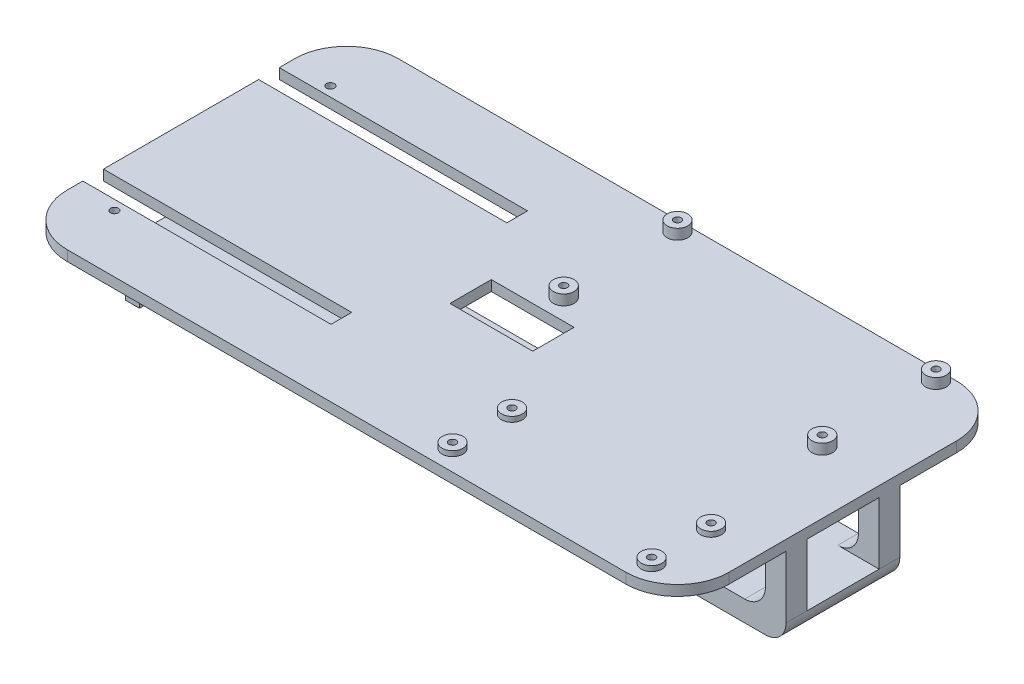
SolidWorks part; units mm, degrees
material "Polycarbonate"
ref_plane "Front Plane" through (0, 0, 0) normal (0, 0, 1) x (1, 0, 0)
ref_plane "Top Plane" through (0, 0, 0) normal (0, 1, 0) x (1, 0, 0)
ref_plane "Right Plane" through (0, 0, 0) normal (1, 0, 0) x (0, 0, -1)
sketch "Sketch1" plane through (0, 0, 0) normal (0, 1, 0) x (1, 0, 0)
  line L1 (-101.6, 17.4625) -> (101.6, 17.4625)
  line L2 (-101.6, 17.4625) -> (-101.6, -17.4625)
  line L3 (-101.6, -17.4625) -> (101.6, -17.4625)
  line L4 (101.6, 17.4625) -> (101.6, -17.4625)
  line L5 (-101.6, 17.4625) -> (101.6, -17.4625) construction
  line L6 (-101.6, -17.4625) -> (101.6, 17.4625) construction
  point P0 (0, 0)
  dimension "D1" = 34.925
  dimension "D2" = 203.2
extrude "Boss-Extrude1" add sketch "Sketch1" along normal blind 6.35
sketch "Sketch2" plane through (0, 6.35, 0) normal (0, 1, 0) x (1, 0, 0)
  line L0 (101.6, -17.4625) -> (101.6, 17.4625) construction
  line L1 (-101.6, -50.8) -> (101.6, -50.8)
  line L2 (-101.6, -50.8) -> (-101.6, 50.8)
  line L3 (-101.6, 50.8) -> (101.6, 50.8)
  line L4 (101.6, -50.8) -> (101.6, 50.8)
  line L5 (-101.6, -50.8) -> (101.6, 50.8) construction
  line L6 (-101.6, 50.8) -> (101.6, -50.8) construction
  point P0 (0, 0)
  dimension "D1" = 101.6
extrude "Boss-Extrude3" add sketch "Sketch2" along normal blind 3.175 from offset 19.05 separate body
sketch "Sketch3" plane through (0, 6.35, 0) normal (0, 1, 0) x (1, 0, 0)
  line L1 (101.6, -17.4625) -> (95.25, -17.4625)
  line L2 (101.6, -17.4625) -> (101.6, -11.1125)
  line L3 (101.6, -11.1125) -> (95.25, -11.1125)
  line L4 (95.25, -17.4625) -> (95.25, -11.1125)
  line L5 (101.6, 17.4625) -> (95.25, 17.4625)
  line L6 (101.6, 17.4625) -> (101.6, 11.1125)
  line L7 (101.6, 11.1125) -> (95.25, 11.1125)
  line L8 (95.25, 17.4625) -> (95.25, 11.1125)
  line L9 (-93.6625, -15.0813) -> (-87.3125, -15.0812)
  line L10 (-93.6625, -15.0813) -> (-93.6625, -10.3188)
  line L11 (-93.6625, -10.3188) -> (-87.3125, -10.3188)
  line L12 (-87.3125, -15.0812) -> (-87.3125, -10.3188)
  line L13 (-101.6, 17.4625) -> (-101.6, -17.4625) construction
  line L15 (-93.6625, 15.0813) -> (-87.3125, 15.0813)
  line L16 (-93.6625, 15.0813) -> (-93.6625, 10.3188)
  line L17 (-93.6625, 10.3188) -> (-87.3125, 10.3188)
  line L18 (-87.3125, 15.0813) -> (-87.3125, 10.3188)
  line L21 (-101.6, -17.4625) -> (101.6, -17.4625) construction
  line L22 (101.6, 17.4625) -> (-101.6, 17.4625) construction
  point P16 (-90.4875, -10.3188)
  point P23 (-87.3125, 12.7)
  point P25 (-90.4875, 15.0813)
  point P29 (-93.6625, -12.7)
  line M9 (101.6, -17.4625) -> (101.6, 17.4625)
  line M10 (101.6, 17.4625) -> (-101.6, 17.4625)
  line M12 (-101.6, -17.4625) -> (101.6, -17.4625)
  dimension "D1" = 6.35
  dimension "D2" = 11.1125
  dimension "D3" = 6.35
  dimension "D4" = 4.7625
  dimension "D5" = 11.1125
  dimension "D6" = 6.35
  dimension "D7" = 4.7625
  dimension "D8" = 4.7625
  dimension "D9" = 4.7625
extrude "Boss-Extrude4" add sketch "Sketch3" along normal up to next contours L4 L3 M12 M9 | L8 L7 M10 M9 region at (98.425, 6.35, -14.2875) region at (98.425, 6.35, 14.2875)
sketch "Sketch4" plane through (0, 28.575, 0) normal (0, 1, 0) x (1, 0, 0)
  line L0 (-101.6, 50.8) -> (-101.6, -50.8) construction
  line L1 (-101.6, -50.8) -> (101.6, -50.8) construction
  line L2 (-101.6, -30.1625) -> (-25.4, -30.1625)
  line L3 (-101.6, -30.1625) -> (-101.6, -23.8125)
  line L4 (-101.6, -23.8125) -> (-25.4, -23.8125)
  line L5 (-25.4, -30.1625) -> (-25.4, -23.8125)
  line L6 (0, 0) -> (-101.6, 0) construction
  line L7 (-25.4, 30.1625) -> (-25.4, 23.8125)
  line L8 (-101.6, 30.1625) -> (-25.4, 30.1625)
  line L9 (-101.6, 30.1625) -> (-101.6, 23.8125)
  line L10 (-101.6, 23.8125) -> (-25.4, 23.8125)
  dimension "D1" = 20.6375
  dimension "D2" = 6.35
  dimension "D3" = 76.2
extrude "Cut-Extrude1" cut sketch "Sketch4" against normal blind 3.175
sketch "Sketch5" plane through (101.6, 0, 0) normal (1, 0, 0) x (0, 0, -1)
  line L1 (14.8971, 25.4) -> (14.8971, 36.7665)
  line L3 (17.4625, 25.4) -> (17.4625, 0) construction
  line L5 (-10.1346, 32.004) -> (-10.1346, 25.4)
  line L6 (10.0076, 25.4) -> (10.0076, 32.004)
  line L7 (-14.8971, 25.4) -> (-10.1346, 25.4)
  line L8 (10.0076, 25.4) -> (14.8971, 25.4)
  line L11 (-50.8, 25.4) -> (-17.4625, 25.4) construction
  line L12 (-46.0375, 25.4) -> (-42.8625, 25.4)
  line L13 (-46.0375, 25.4) -> (-46.0375, 22.225)
  line L14 (-46.0375, 22.225) -> (-42.8625, 22.225)
  line L15 (-42.8625, 25.4) -> (-42.8625, 22.225)
  line L16 (-11.1125, 6.35) -> (11.1125, 6.35) construction
  line L21 (17.4625, 25.4) -> (50.8, 25.4) construction
  line L22 (-14.8971, 25.4) -> (-14.8971, 36.7665)
  line L23 (-50.8, 28.575) -> (-50.8, 25.4) construction
  line L24 (42.8625, 25.4) -> (46.0375, 25.4)
  line L25 (42.8625, 25.4) -> (42.8625, 22.225)
  line L26 (42.8625, 22.225) -> (46.0375, 22.225)
  line L27 (46.0375, 25.4) -> (46.0375, 22.225)
  line L28 (-14.8971, 36.7665) -> (-3.7846, 36.7665)
  line L29 (50.8, 28.575) -> (50.8, 25.4) construction
  line L30 (-3.7846, 36.7665) -> (-3.7846, 32.004)
  line L31 (-3.7846, 32.004) -> (-10.1346, 32.004)
  line L32 (14.8971, 36.7665) -> (3.6576, 36.7665)
  line L33 (3.6576, 36.7665) -> (3.6576, 32.004)
  line L34 (3.6576, 32.004) -> (10.0076, 32.004)
  line L35 (-17.4625, 25.4) -> (-17.4625, 0) construction
  point P31 (-46.0375, 23.8125)
  point P38 (17.4625, 12.7)
  dimension "D2" = 6.604
  dimension "D3" = 2.5654
  dimension "D4" = 3.175
  dimension "D5" = 3.175
  dimension "D6" = 4.7625
  dimension "D7" = 4.7625
  dimension "D8" = 3.175
  dimension "D9" = 3.175
  dimension "D10" = 19.05
  dimension "D11" = 4.7625
  dimension "D12" = 4.7625
  dimension "D13" = 6.35
  dimension "D14" = 4.8895
  dimension "D15" = 6.35
  dimension "D16" = 4.7625
  dimension "D17" = 2.5654
extrude "Boss-Extrude5" add sketch "Sketch5" against normal blind 3.175 from offset 190.5 contours L15 L14 L13 L12 | L27 L26 L25 L24 offset against normal yes
hole_wizard "#2 Clearance Hole1" positions "Sketch7" profile "Sketch8" hole size "#2" standard "ANSI Inch" end condition through all
sketch "Sketch7" plane through (0, 25.4, 0) normal (0, -1, 0) x (-1, 0, 0)
  line L12 (25.4, 30.1625) -> (101.6, 30.1625) construction
  line L13 (101.6, 50.8) -> (101.6, 30.1625) construction
  line L14 (101.6, -30.1625) -> (101.6, -50.8) construction
  line L15 (101.6, -30.1625) -> (25.4, -30.1625) construction
  point P20 (88.9, 33.147)
  point P69 (88.9, -33.147)
  dimension "D1" = 2.9845
  dimension "D2" = 12.7
  dimension "D3" = 12.7
  dimension "D4" = 2.9845
sketch "Sketch8" plane through (-88.9, 25.4, -33.147) normal (1, 0, 0) x (0, 0, -1)
  line L0 (0, 0) -> (0, 3.175)
  line L1 (0, 3.175) -> (1.2192, 3.175)
  line L2 (1.2192, 3.175) -> (1.2192, 0)
  line L5 (1.2192, 0) -> (0, 0)
  line L11 (0, -6.35) -> (0, 107.95) construction
  dimension "Thru Hole Dia." = 2.4384
  dimension "Thru Hole Depth" = 3.175
fillet "Fillet1" radius 15.875 2 edges at (101.6, 26.9875, -50.8) (101.6, 26.9875, 50.8)
fillet "Fillet2" radius 6.35 3 edges at (95.25, 6.35, 14.2875) (95.25, 6.35, -14.2875) (101.6, 0, 0)
hole_wizard "#4-40 Tapped Hole2" positions "Sketch12" profile "Sketch14" tap size "#4-40" standard "ANSI Inch" end condition through all
sketch "Sketch12" plane through (0, 25.4, 0) normal (0, -1, 0) x (-1, 0, 0)
  line L0 (-26.1937, -44.45) -> (-87.3125, -44.45) construction
  line L2 (101.6, -50.8) -> (-85.725, -50.8) construction
  line L3 (-101.6, -34.925) -> (-101.6, -17.4625) construction
  line L4 (-26.1937, -44.45) -> (-26.1937, -26.1937) construction
  line L6 (-26.1937, -26.1937) -> (-87.3125, -26.1938) construction
  line L7 (-87.3125, -26.1938) -> (-87.3125, -44.45) construction
  line L8 (101.6, -50.8) -> (-85.725, -50.8) construction
  point P0 (-87.3125, -44.45)
  point P3 (-87.3125, -26.1938)
  point P6 (-26.1937, -26.1937)
  point P9 (-26.1937, -44.45)
  dimension "D1" = 61.1187
  dimension "D2" = 6.35
  dimension "D3" = 14.2875
  dimension "D4" = 24.6062
sketch "Sketch14" plane through (87.3125, 25.4, 44.45) normal (1, 0, 0) x (0, 0, -1)
  line L0 (0, 0) -> (0, 3.175)
  line L1 (0, 3.175) -> (1.1303, 3.175)
  line L2 (1.1303, 3.175) -> (1.1303, 0)
  line L5 (1.1303, 0) -> (0, 0)
  line L11 (0, -6.35) -> (0, 107.95) construction
  dimension "Thru Tap Drill Dia." = 2.2606
  dimension "Thru Tap Drill Depth" = 3.175
cosmetic thread "Hole Thread5" parameters "D2"=2.8448
cosmetic thread "Hole Thread6" parameters "D2"=2.8448
cosmetic thread "Hole Thread7" parameters "D2"=2.8448
cosmetic thread "Hole Thread8" parameters "D2"=2.8448
sketch "Sketch15" plane through (0, 25.4, 0) normal (0, -1, 0) x (1, 0, 0)
  circle A0 centre (26.1937, 44.45) radius 3.175
  circle A1 centre (87.3125, 44.45) radius 3.175
  circle A2 centre (87.3125, 26.1938) radius 3.175
  circle A3 centre (26.1937, 26.1937) radius 3.175
  dimension "D1" = 6.35
extrude "Boss-Extrude6" add sketch "Sketch15" against normal blind 1.5875 from surface starting at face at (87.3125, 28.575, 43.3197)
hole_wizard "#4-40 Tapped Hole4" positions "Sketch19" profile "Sketch20" tap size "#4-40" standard "ANSI Inch" end condition through all
sketch "Sketch19" plane through (0, 28.575, 0) normal (0, -1, 0) x (-1, 0, 0)
  point P0 (-87.3125, -44.45)
  point P3 (-87.3125, -26.1938)
  point P6 (-26.1937, -26.1937)
  point P9 (-26.1937, -44.45)
sketch "Sketch20" plane through (87.3125, 28.575, 44.45) normal (1, 0, 0) x (0, 0, -1)
  line L0 (0, 0) -> (0, 1.5875)
  line L1 (0, 1.5875) -> (1.1303, 1.5875)
  line L2 (1.1303, 1.5875) -> (1.1303, 0)
  line L5 (1.1303, 0) -> (0, 0)
  line L11 (0, -6.35) -> (0, 107.95) construction
  dimension "Thru Tap Drill Dia." = 2.2606
  dimension "Thru Tap Drill Depth" = 1.5875
sketch "Sketch22" plane through (-101.6, 0, 0) normal (-1, 0, 0) x (0, 0, 1)
  line L0 (12.7476, -6.477) -> (12.7476, -9.652)
  line L5 (-17.4625, 0) -> (17.4625, 0) construction
  line L6 (17.0656, 0) -> (12.7476, 0)
  line L7 (17.0656, 0) -> (17.0656, -9.652)
  line L8 (17.0656, -9.652) -> (7.9851, -9.652) construction
  line L9 (12.7476, 0) -> (12.7476, -6.477)
  line L10 (17.4625, 6.35) -> (17.4625, 0) construction
  line L12 (7.9851, -9.652) -> (7.9851, -6.477) construction
  line L13 (7.9851, -6.477) -> (12.7476, -6.477) construction
  line L14 (0, 0) -> (0, -14.0919) construction
  line L15 (-7.9851, -6.477) -> (-12.7476, -6.477) construction
  line L16 (-7.9851, -9.652) -> (-7.9851, -6.477) construction
  line L17 (-12.7476, 0) -> (-12.7476, -6.477)
  line L18 (-17.0656, -9.652) -> (-7.9851, -9.652) construction
  line L19 (-17.0656, 0) -> (-17.0656, -9.652)
  line L20 (-17.0656, 0) -> (-12.7476, 0)
  line L21 (12.7476, -9.652) -> (17.0656, -9.652)
  line L22 (-12.7476, -6.477) -> (-12.7476, -9.652)
  line L23 (-12.7476, -9.652) -> (-17.0656, -9.652)
  dimension "D1" = 4.318
  dimension "D2" = 0.3969
  dimension "D3" = 9.652
  dimension "D4" = 3.175
  dimension "D5" = 4.7625
extrude "Boss-Extrude11" add sketch "Sketch22" against normal blind 4.318
fillet "Fillet14" radius 15.875 2 edges at (-101.6, 26.9875, 50.8) (-101.6, 26.9875, -50.8)
sketch "Sketch23" plane through (0, 28.575, 0) normal (0, 1, 0) x (1, 0, 0)
  line L0 (101.6, -34.925) -> (101.6, 34.925) construction
  line L1 (82.55, 12.7) -> (3.175, 12.7) construction
  line L2 (82.55, 12.7) -> (82.55, 47.625) construction
  line L3 (82.55, 47.625) -> (3.175, 47.625) construction
  line L4 (3.175, 12.7) -> (3.175, 47.625) construction
  line L5 (85.725, 50.8) -> (-85.725, 50.8) construction
  circle A0 centre (3.175, 12.7) radius 3.175
  circle A1 centre (3.175, 47.625) radius 3.175
  circle A2 centre (82.55, 12.7) radius 3.175
  circle A3 centre (82.55, 47.625) radius 3.175
  dimension "D1" = 79.375
  dimension "D2" = 34.925
  dimension "D3" = 19.05
  dimension "D4" = 3.175
extrude "Boss-Extrude12" add sketch "Sketch23" along normal blind 3.175
sketch "Sketch26" plane through (0, 28.575, 0) normal (0, 1, 0) x (1, 0, 0)
  line L1 (-12.7, -6.35) -> (12.7, -6.35)
  line L2 (-12.7, -6.35) -> (-12.7, 6.35)
  line L3 (-12.7, 6.35) -> (12.7, 6.35)
  line L4 (12.7, -6.35) -> (12.7, 6.35)
  line L5 (-12.7, -6.35) -> (12.7, 6.35) construction
  line L6 (-12.7, 6.35) -> (12.7, -6.35) construction
  point P0 (0, 0)
  dimension "D1" = 25.4
  dimension "D2" = 12.7
extrude "Cut-Extrude2" cut sketch "Sketch26" against normal up to next
hole_wizard "#4-40 Tapped Hole3" positions "Sketch28" profile "Sketch29" tap size "#4-40" standard "ANSI Inch" end condition up to next
sketch "Sketch28" plane through (0, 31.75, 0) normal (0, 1, 0) x (1, 0, 0)
  point P0 (3.175, 47.625)
  point P3 (3.175, 12.7)
  point P6 (82.55, 12.7)
  point P9 (82.55, 47.625)
sketch "Sketch29" plane through (3.175, 31.75, -47.625) normal (1, 0, 0) x (0, 0, 1)
  line L0 (0, 0) -> (0, 6.35)
  line L1 (0, 6.35) -> (1.1303, 6.35)
  line L2 (1.1303, 6.35) -> (1.1303, 0)
  line L5 (1.1303, 0) -> (0, 0)
  line L11 (0, -6.35) -> (0, 107.95) construction
  dimension "Thru Tap Drill Dia." = 2.2606
  dimension "Thru Tap Drill Depth" = 6.35
cosmetic thread "Hole Thread9" parameters "D2"=2.8448
cosmetic thread "Hole Thread10" parameters "D2"=2.8448
cosmetic thread "Hole Thread11" parameters "D2"=2.8448
cosmetic thread "Hole Thread12" parameters "D2"=2.8448
hole_wizard "M1.2x0.25 Tapped Hole1" positions "Sketch30" profile "Sketch31" tap size "M1.2x0.25" standard "ANSI Metric"
sketch "Sketch30" plane through (0, -9.652, 0) normal (0, -1, 0) x (-1, 0, 0)
  line L0 (101.6, 17.0656) -> (101.6, 12.7476) construction
  line L1 (97.282, 12.7476) -> (101.6, 12.7476) construction
  line L2 (97.282, -12.7476) -> (101.6, -12.7476) construction
  line L3 (101.6, -12.7476) -> (101.6, -17.0656) construction
  point P0 (99.441, 14.9066)
  point P2 (99.441, -14.9066)
  point P8 (101.6, 14.9066)
  point P12 (99.441, 12.7476)
  point P16 (99.441, -12.7476)
  point P20 (101.6, -14.9066)
sketch "Sketch31" plane through (-99.441, -9.652, -14.9066) normal (1, 0, 0) x (0, 0, -1)
  line L0 (0, 0) -> (0, 5.3654)
  line L1 (0, 5.3654) -> (0.475, 5.08)
  line L2 (0.475, 5.08) -> (0.475, 0)
  line L5 (0.475, 0) -> (0, 0)
  line L10 (0, 5.3654) -> (-0.475, 5.08) construction
  line L11 (0, -6.35) -> (0, 107.95) construction
  dimension "Tap Drill Dia." = 0.95
  dimension "Tap Drill Depth" = 5.08
  dimension "Drill Angle" = 118
cosmetic thread "Hole Thread13" parameters "D1"=2.286, "D2"=1.2
cosmetic thread "Hole Thread14" parameters "D1"=2.286, "D2"=1.2
